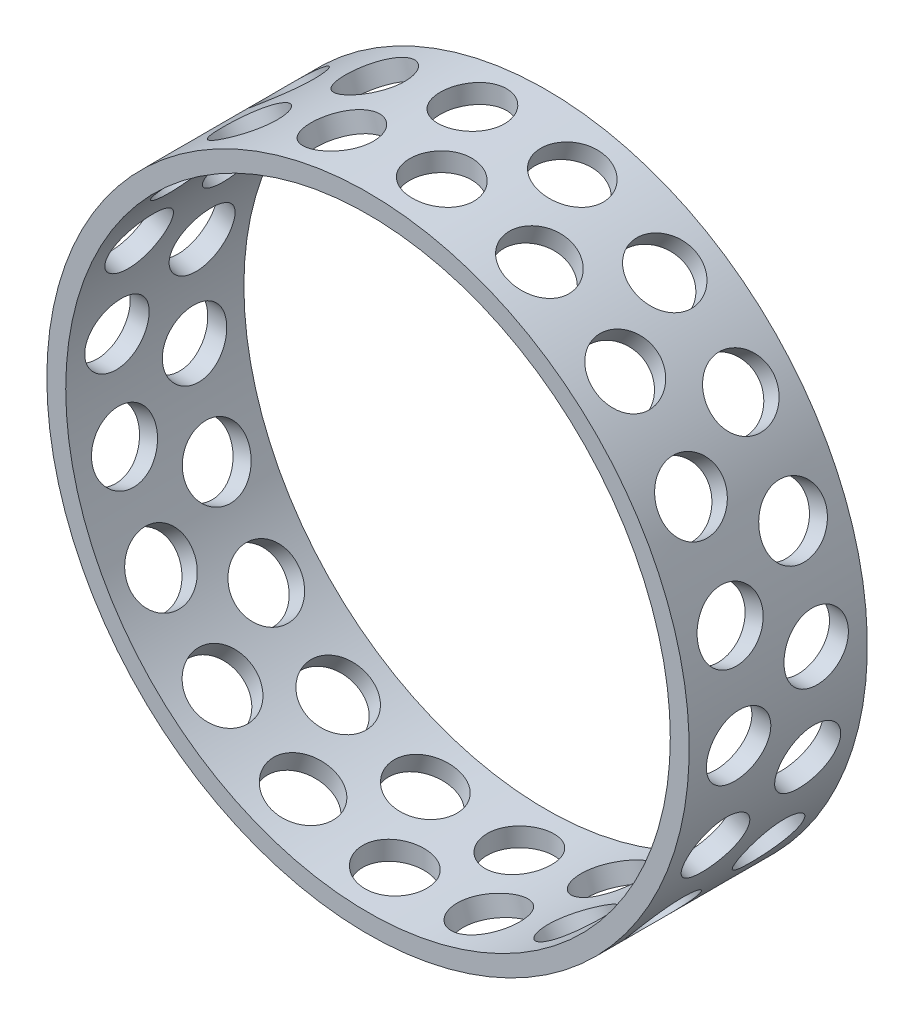
SolidWorks part; units mm, degrees
ref_plane "Front Plane" through (0, 0, 0) normal (0, 0, 1) x (1, 0, 0)
ref_plane "Top Plane" through (0, 0, 0) normal (0, 1, 0) x (1, 0, 0)
ref_plane "Right Plane" through (0, 0, 0) normal (1, 0, 0) x (0, 0, -1)
sketch "Sketch1" plane through (0, 0, 0) normal (1, 0, 0) x (0, 0, -1)
  line L0 (1, 84.9998) -> (48.15, 84.9998)
  line L1 (48.15, 84.9998) -> (48.15, 79.9998)
  line L2 (48.15, 79.9998) -> (1, 79.9998)
  line L3 (1, 79.9998) -> (1, 84.9998)
  dimension "D1" = 84.9998
  dimension "D2" = 5
  dimension "D3" = 47.15
  dimension "D4" = 1
ref_axis "Axis1" through (0, 0, -50.5075) along (0, 0, 1)
revolve "Revolve1" add sketch "Sketch1" angle 360 about axis through (0, 0, -50.5075) along (0, 0, 1)
sketch "Sketch2" plane through (0, 0, 0) normal (1, 0, 0) x (0, 0, -1)
  line L0 (14.3098, 6.2149) -> (24.575, 0) construction
  line L1 (50.5075, 0) -> (-1.3575, 0) construction
  line L2 (24.575, 0) -> (34.8402, -6.2149) construction
  line L3 (1, 84.9998) -> (1, -84.9998) construction
  circle A0 centre (14.3098, 6.2149) radius 8.5
  circle A1 centre (34.8402, -6.2149) radius 8.5
  dimension "D1" = 17
  dimension "D2" = 12
  dimension "D3" = 23.575
extrude "Cut-Extrude1" cut sketch "Sketch2" against normal through all
pattern_circular "CirPattern1" count 20 over 360 about axis through (0, 0, -50.5075) along (0, 0, 1) of "Cut-Extrude1"
